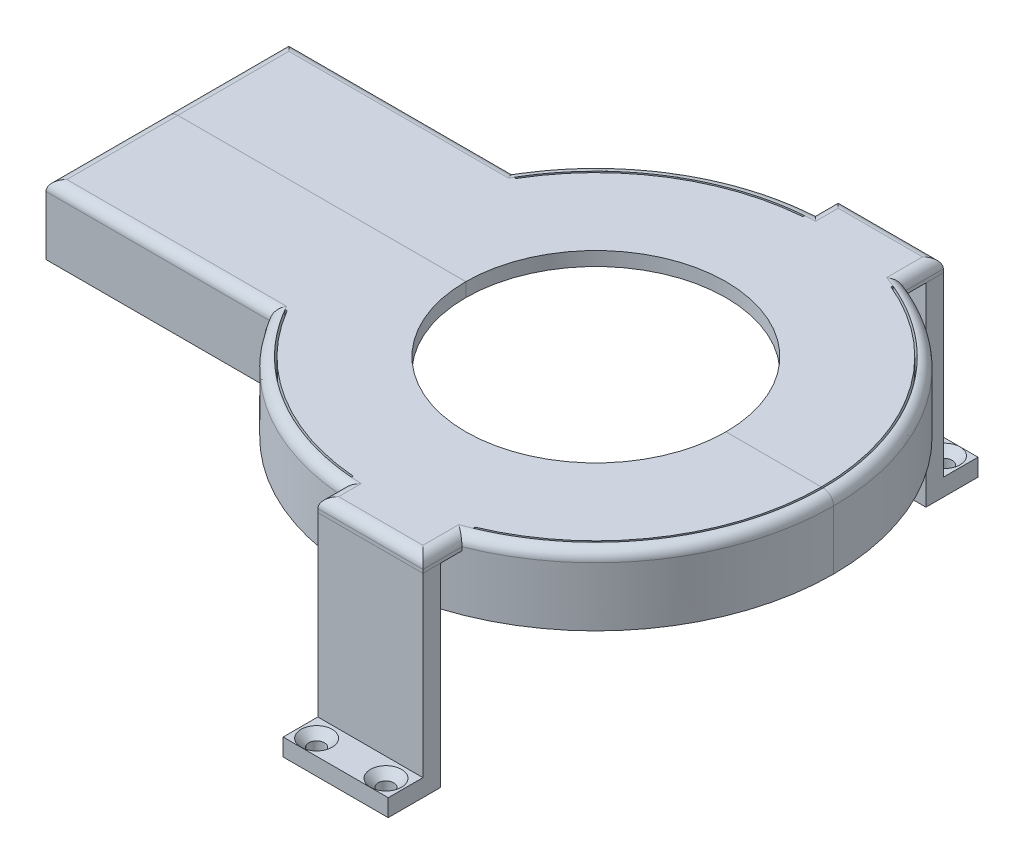
SolidWorks part; units mm, degrees
ref_plane "Front Plane" through (0, 0, 0) normal (0, 0, 1) x (1, 0, 0)
ref_plane "Top Plane" through (0, 0, 0) normal (0, 1, 0) x (1, 0, 0)
ref_plane "Right Plane" through (0, 0, 0) normal (1, 0, 0) x (0, 0, -1)
ref_axis "Axis1" through (0, -44.5658, 0) along (0, 1, 0)
sketch "Sketch14" plane through (0, 0, 0) normal (0, 1, 0) x (1, 0, 0)
  line L1 (-5.1463, -75) -> (25.1463, -75)
  line L2 (-5.1463, -75) -> (-5.1463, -70)
  line L3 (-5.1463, -70) -> (25.1463, -70)
  line L4 (25.1463, -75) -> (25.1463, -70)
  line L5 (-5.1463, -75) -> (25.1463, -70) construction
  line L6 (-5.1463, -70) -> (25.1463, -75) construction
  line L7 (-49.8606, 0) -> (49.8606, 0) construction
  line L8 (0, -55) -> (0, 55) construction
  point P0 (10, -72.5)
  dimension "D1" = 70
  dimension "D2" = 5
  dimension "D3" = 10
extrude "Boss-Extrude3" add sketch "Sketch14" against normal blind 51
sketch "Sketch15" plane through (0, 0, 0) normal (0, 1, 0) x (1, 0, 0)
  line L0 (-37.5, 0) -> (-65, 0)
  line L1 (37.5, 0) -> (65, 0)
  line L2 (-65, 0) -> (-120.5, 0)
  line L3 (-120.5, 0) -> (-120.5, -33)
  line L4 (-120.5, -33) -> (-56, -33)
  arc A0 (-56, -33) -> (65, 0) centre (0, 0) ccw
  arc A1 (-37.5, 0) -> (37.5, 0) centre (0, 0) ccw
  dimension "D1" = 75
  dimension "D2" = 130
  dimension "D3" = 83
  dimension "D4" = 33
extrude "Boss-Extrude4" add sketch "Sketch15" along normal blind 4
sketch "Sketch16" plane through (0, -51, 0) normal (0, -1, 0) x (1, 0, 0)
  line L1 (-5.1463, 70) -> (25.1463, 70)
  line L2 (-5.1463, 70) -> (-5.1463, 85)
  line L3 (-5.1463, 85) -> (25.1463, 85)
  line L4 (25.1463, 70) -> (25.1463, 85)
  dimension "D1" = 15
extrude "Boss-Extrude5" add sketch "Sketch16" along normal blind 5
hole_wizard "CSK for M4 Hex Socket Countersunk Head1" positions "Sketch17" profile "Sketch18" countersink size "M4" standard "BSI" end condition through all
sketch "Sketch17" plane through (0, -51, 0) normal (0, 1, 0) x (1, 0, 0)
  line L0 (0, -33) -> (0, 33) construction
  line L1 (-5.1463, -75) -> (25.1463, -75) construction
  point P0 (20, -80.5)
  point P3 (0, -80.5)
  dimension "D1" = 20
  dimension "D2" = 0
  dimension "D3" = 5.5
  dimension "D4" = 5.5
sketch "Sketch18" plane through (20, -51, 80.5) normal (1, 0, 0) x (0, 0, 1)
  line L0 (0, 0) -> (0, 5)
  line L1 (0, 5) -> (2.25, 5)
  line L2 (2.25, 5) -> (2.25, 2.23)
  line L3 (2.25, 2.23) -> (4.48, 0)
  line L5 (4.48, 0) -> (0, 0)
  line L6 (-2.25, 2.23) -> (-4.48, 0) construction
  line L11 (0, -6.35) -> (0, 107.95) construction
  dimension "Thru Hole Dia." = 4.5
  dimension "Thru Hole Depth" = 5
  dimension "Near C'Sink Dia." = 8.96
  dimension "Near C'Sink Angle" = 90
sketch "Sketch19" plane through (0, 0, 0) normal (0, 1, 0) x (1, 0, 0)
  line L1 (-5.1463, -75) -> (25.1463, -75)
  line L2 (-5.1463, -75) -> (-5.1463, -59.1173)
  line L3 (-5.1463, -59.1173) -> (25.1463, -59.1173)
  line L4 (25.1463, -75) -> (25.1463, -59.1173)
extrude "Boss-Extrude6" add sketch "Sketch19" along normal blind 4
sketch "Sketch20" plane through (0, 4, 0) normal (0, 1, 0) x (1, 0, 0)
  line L0 (-120.5, 0) -> (-123.5, 0)
  line L1 (-123.5, 0) -> (-123.5, -34.9997)
  line L4 (-56.5774, -33) -> (-120.5, -33)
  line L5 (-120.5, -33) -> (-120.5, 0)
  line L6 (65.4981, 0) -> (68.5265, 0)
  line L7 (-123.5, -34.9997) -> (-58.9143, -34.9997)
  arc A0 (-56.5774, -33) -> (65.4981, 0) centre (0, 0) ccw
  arc A1 (-58.9143, -34.9997) -> (68.5265, 0) centre (0, 0) ccw
  dimension "D1" = 3
extrude "Boss-Extrude7" add sketch "Sketch20" against normal blind 20
fillet "Fillet6" radius 3 7 edges at (56.6527, 4, 38.5532) (25.1463, 4, 69.373) (10, 4, 75) (-5.1463, 4, 71.6665) (-36.107, 4, 58.2423) (-123.5, 4, 17.4998) (-91.2072, 4, 34.9997)
mirror "Mirror35" about plane through (0, 0, 0) normal (0, 0, 1) of bodies 137 131 134
